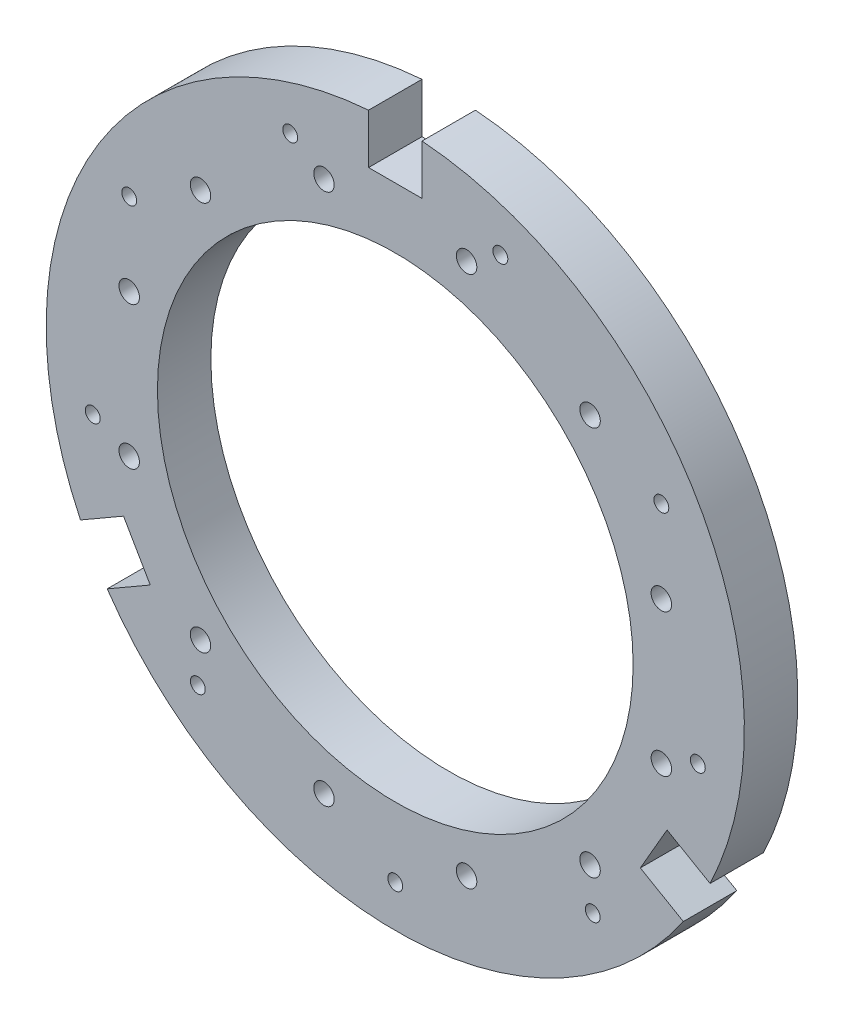
SolidWorks part; units mm, degrees
material "Zoltek Panex 33"
ref_plane "Plan de face" through (0, 0, 0) normal (0, 0, 1) x (1, 0, 0)
ref_plane "Plan de dessus" through (0, 0, 0) normal (0, 1, 0) x (1, 0, 0)
ref_plane "Plan de droite" through (0, 0, 0) normal (1, 0, 0) x (0, 0, -1)
sketch "Esquisse1" plane through (0, 0, 0) normal (0, 0, 1) x (1, 0, 0)
  line L0 (5.741, 64.1) -> (5.741, 50.7765) construction
  line L1 (52.6417, -37.0219) -> (61.8908, -42.3618)
  line L2 (0, 51.1) -> (0, 0) construction
  line L3 (58.3827, -27.0781) -> (67.6318, -32.4181)
  line L4 (0, 51.1) -> (5.741, 51.1) construction
  line L5 (5.741, 64.1) -> (5.741, 74.7799)
  line L6 (5.741, 64.1) -> (-5.741, 64.1)
  line L7 (-5.741, 64.1) -> (-5.741, 74.7799)
  line L8 (52.6417, -37.0219) -> (58.3827, -27.0781)
  line L9 (-58.3827, -27.0781) -> (-67.6318, -32.4181)
  line L10 (-52.6417, -37.0219) -> (-61.8908, -42.3618)
  line L11 (-58.3827, -27.0781) -> (-52.6417, -37.0219)
  arc A0 (5.741, 74.7799) -> (67.6318, -32.4181) centre (0, 0) cw
  circle A1 centre (0, 0) radius 75 construction
  circle A2 centre (0, 0) radius 51.1
  arc A4 (-5.741, 74.7799) -> (-67.6318, -32.4181) centre (0, 0) ccw
  arc A5 (-61.8908, -42.3618) -> (61.8908, -42.3618) centre (0, 0) ccw
  point P22 (0, 0)
  dimension "D4" = 150
  dimension "D6" = 102.2
  dimension "D2" = 5.741
  dimension "D5" = 11.482
  dimension "D7" = 13
  dimension "D1" = 3
extrude "Boss.-Extru.1" add sketch "Esquisse1" along normal blind 11.482 contours L10 A5 L1 L8 L3 A0 L5 L6 L7 A4 L9 L11 A2
sketch "Sketch2" plane through (0, 0, 11.482) normal (0, 0, 1) x (1, 0, 0)
  line L0 (0, 0) -> (0, 96.9743) construction
  line L1 (0, 0) -> (22.5733, 62.0197) construction
  line L2 (22.5733, 62.0197) -> (38.7609, 106.4946) construction
  circle A0 centre (22.5733, 62.0197) radius 1.6
  dimension "D2" = 3.2
  dimension "D1" = 66
  dimension "D5" = 20
extrude "Cut-Extrude1" cut sketch "Sketch2" against normal through all
ref_axis "Axis1" through (0, 0, -0.5741) along (0, 0, 1)
pattern_circular "CirPattern1" count 9 over 360 about axis through (0, 0, -0.5741) along (0, 0, 1) of "Cut-Extrude1" reverse direction yes
sketch "Sketch3" plane through (0, 0, 0) normal (0, 0, 1) x (1, 0, 0)
  line L0 (0, 0) -> (0, 40) construction
  line L1 (0, 0) -> (15.3169, 57.1635) construction
  circle A0 centre (15.3169, 57.1635) radius 2.2
  dimension "D4" = 4.4
  dimension "D1" = 40
  dimension "D2" = 15
  dimension "D3" = 59.18
extrude "Cut-Extrude2" cut sketch "Sketch3" against normal mid plane 50
pattern_circular "CirPattern2" count 12 over 360 about axis through (0, 0, -0.5741) along (0, 0, 1) of "Cut-Extrude2"
equation "\"d_i_tube\"= 150mm'Inner Rocket Body Composite Tube Diameter"
equation "\"t_tube\"= 1.182mm'Thickness of Rocket Body Composite Tube"
equation "\"l_upper_body_tube\"= 949.3mm'Upper Rocket Body Composite Tube length"
equation "\"l_lower_body_tube\"= 816mm'Lower Rocket Body Composite Tube Length"
equation "\"d_a_NC\"= 154mm'Outer Diameter of Nosecone base"
equation "\"d_i_phenolic_tube\"= 152.3mm'Inner Phenolic Tube Diameter"
equation "\"t_phenolic_tube\"= 2mm'Thickness of Phenolic Body Tube"
equation "\"l_fin_cut\"= 220mm'Length of fin on Motor Retainer"
equation "\"t_SW-Panel\"= 11.482mm'Thickness of Sandwich-Panel"
equation "\"l_motor_tube\"=610mm'Length of phenolic motor tube"
equation "\"d_i_motor_tube\"=99.06mm'Inner diameter of phenolic motor tube"
equation "\"t_motor_tube\"=1.58mm'Thicknes of phenolic motor tube"
equation "\"D4@Esquisse1\"=\"d_i_tube\""
equation "\"D6@Esquisse1\"=102.2"
equation "\"D2@Esquisse1\"=\"t_SW-Panel\"/2"
equation "\"D5@Esquisse1\"=\"t_SW-Panel\""
equation "\"D1@Boss.-Extru.1\"=\"t_SW-Panel\""
